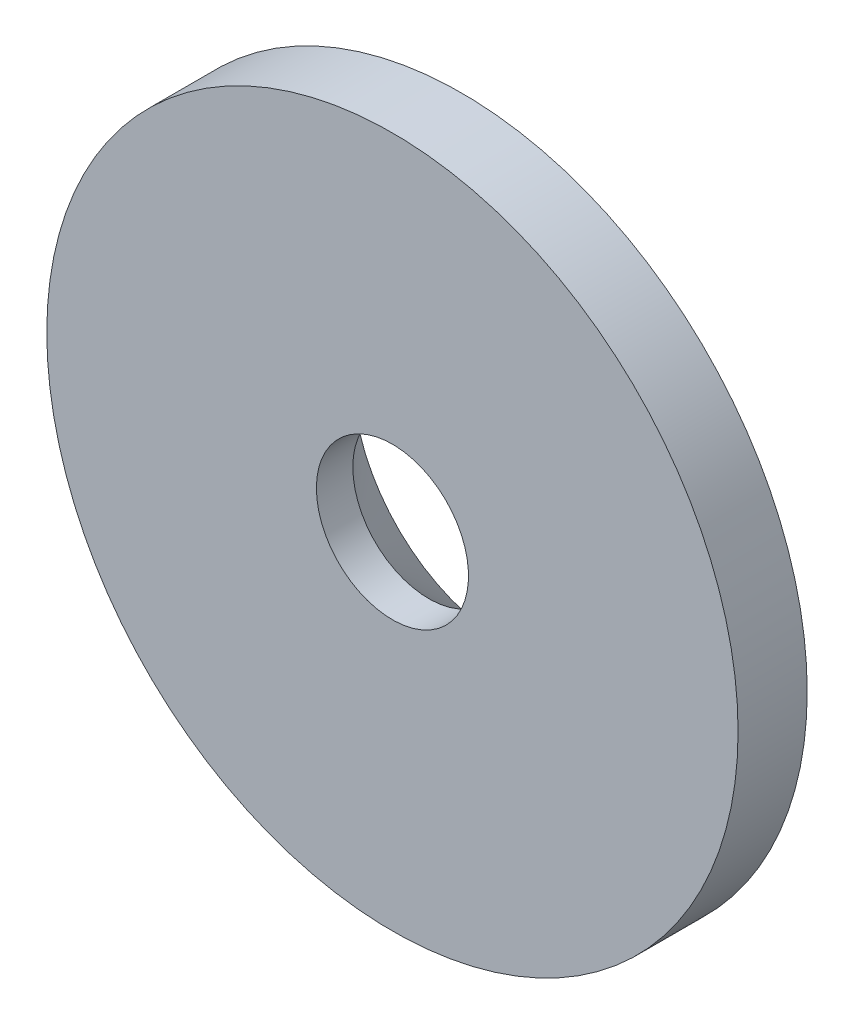
SolidWorks part; units mm, degrees
material "AISI 316 (1.4401)"
ref_plane "Płaszczyzna przednia" through (0, 0, 0) normal (0, 0, 1) x (1, 0, 0)
ref_plane "Płaszczyzna górna" through (0, 0, 0) normal (0, 1, 0) x (1, 0, 0)
ref_plane "Płaszczyzna prawa" through (0, 0, 0) normal (1, 0, 0) x (0, 0, -1)
sketch "Szkic1" plane through (0, 0, 0) normal (1, 0, 0) x (0, 0, -1)
  line L0 (0, 0) -> (5, 0) construction
  line L1 (0, 0) -> (0, 15)
  line L2 (0, 15) -> (3, 15)
  line L3 (3, 15) -> (5, 11)
  line L4 (5, 11) -> (5, 0)
  line L5 (0, 0) -> (5, 0)
  dimension "D1" = 30
  dimension "D2" = 5
  dimension "D3" = 4
  dimension "D4" = 2
revolve "Obrót1" add sketch "Szkic1" angle 360 about L0
hole_wizard "Pogłębienie stożkowe pod M6 Wkręt z łbem stożkowym płaskim1" positions "Szkic2" profile "Szkic3" countersink size "M6" standard "ISO" end condition up to next
sketch "Szkic2" plane through (0, 0, -5) normal (0, 0, -1) x (-1, 0, 0)
  point P0 (0, 0)
sketch "Szkic3" plane through (0, 0, -5) normal (1, 0, 0) x (0, 1, 0)
  line L0 (0, 0) -> (0, 5)
  line L1 (0, 5) -> (3.3, 5)
  line L2 (3.3, 5) -> (3.3, 3.42)
  line L3 (3.3, 3.42) -> (6.72, 0)
  line L5 (6.72, 0) -> (0, 0)
  line L6 (-3.3, 3.42) -> (-6.72, 0) construction
  line L11 (0, -6.35) -> (0, 107.95) construction
  dimension "Średnica otworu na wylot" = 6.6
  dimension "Głębokość otworu na wylot" = 5
  dimension "Średnica zewnętrznego pogłębienia stożkowego" = 13.44
  dimension "Kąt zewnętrznego pogłębienia stożkowego" = 90
